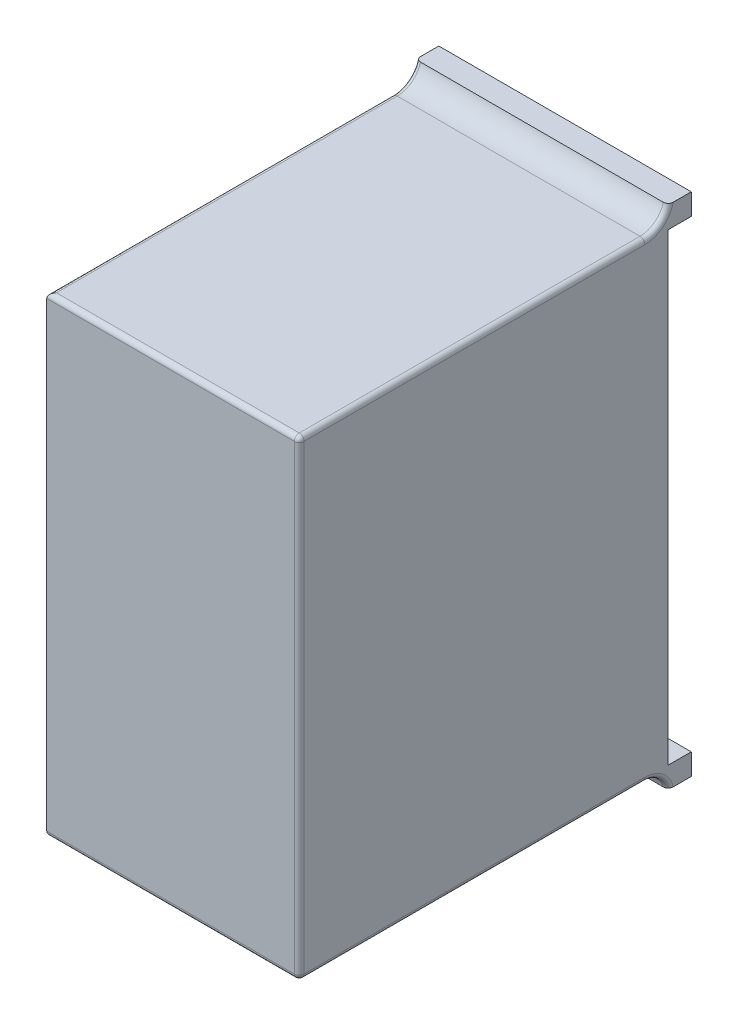
SolidWorks part; units mm, degrees
ref_plane "Front Plane" through (0, 0, 0) normal (1, 0, 0) x (0, 1, 0)
ref_plane "Top Plane" through (0, 0, 0) normal (0, 0, 1) x (0, 1, 0)
ref_plane "Right Plane" through (0, 0, 0) normal (0, 1, 0) x (-1, 0, 0)
sketch "Sketch1" plane through (0, 0, 0) normal (1, 0, 0) x (0, 1, 0)
  line L1 (0, 0) -> (194, 0)
  line L2 (0, 0) -> (0, -152)
  line L3 (0, -152) -> (194, -152)
  line L4 (194, 0) -> (194, -152)
  dimension "D1" = 152
  dimension "D2" = 194
extrude "Boss-Extrude1" add sketch "Sketch1" along normal blind 104
shell "Shell1" thickness 1.5 removed face at (52, 97, -152)
sketch "Sketch2" plane through (0, 0, 0) normal (-1, 0, 0) x (0, -1, 0)
  line L0 (-192.5, -1.5) -> (-192.5, -150.5)
  line L1 (-194, 0) -> (0, 0)
  line L2 (-194, 0) -> (-194, -152)
  line L3 (-194, -152) -> (0, -152)
  line L4 (0, 0) -> (0, -152)
  line L6 (-1.5, -1.5) -> (-1.5, -150.5)
  line L7 (-192.5, -1.5) -> (-1.5, -1.5)
  line L8 (-192.5, -150.5) -> (-192.5, -152)
  line L9 (-192.5, -152) -> (-1.5, -152)
  line L10 (-1.5, -152) -> (-1.5, -150.5)
  line L12 (-192.5, -150.5) -> (-1.5, -150.5) construction
  dimension "D1" = 1.5
extrude "Cut-Extrude1" cut sketch "Sketch2" against normal blind 2 contours L0 L8 L9 L10 L6 L7
sketch "Sketch4" plane through (0, 0, -152) normal (0, 0, -1) x (1, 0, 0)
  line L0 (104, 0) -> (104, -194) construction
  line L1 (104, -1.5) -> (0, -1.5)
  line L2 (104, -1.5) -> (104, 7.3)
  line L3 (104, 7.3) -> (0, 7.3)
  line L4 (0, -1.5) -> (0, 7.3)
  line L5 (102.5, -1.5) -> (0, -1.5) construction
  line L6 (0, 0) -> (0, -1.5) construction
  line L8 (0, -192.5) -> (104, -192.5)
  line L9 (0, -192.5) -> (0, -201.3)
  line L10 (0, -201.3) -> (104, -201.3)
  line L11 (104, -192.5) -> (104, -201.3)
  dimension "D1" = 8.8
  dimension "D2" = 8.8
extrude "Boss-Extrude2" add sketch "Sketch4" along normal blind 9.5
fillet "Fillet1" radius 10 2 edges at (52, 0, -152) (52, 194, -152)
fillet "Fillet2" radius 2 11 edges at (104, -2.0313, -148.4129) (0, -2.0313, -148.4129) (0, 196.0313, -148.4129) (104, 196.0313, -148.4129) (52, 0, 0) (104, 0, -71.1857) (0, 0, -71.1857) (104, 97, 0) (52, 194, 0) (0, 194, -71.1857) (104, 194, -71.1857)
